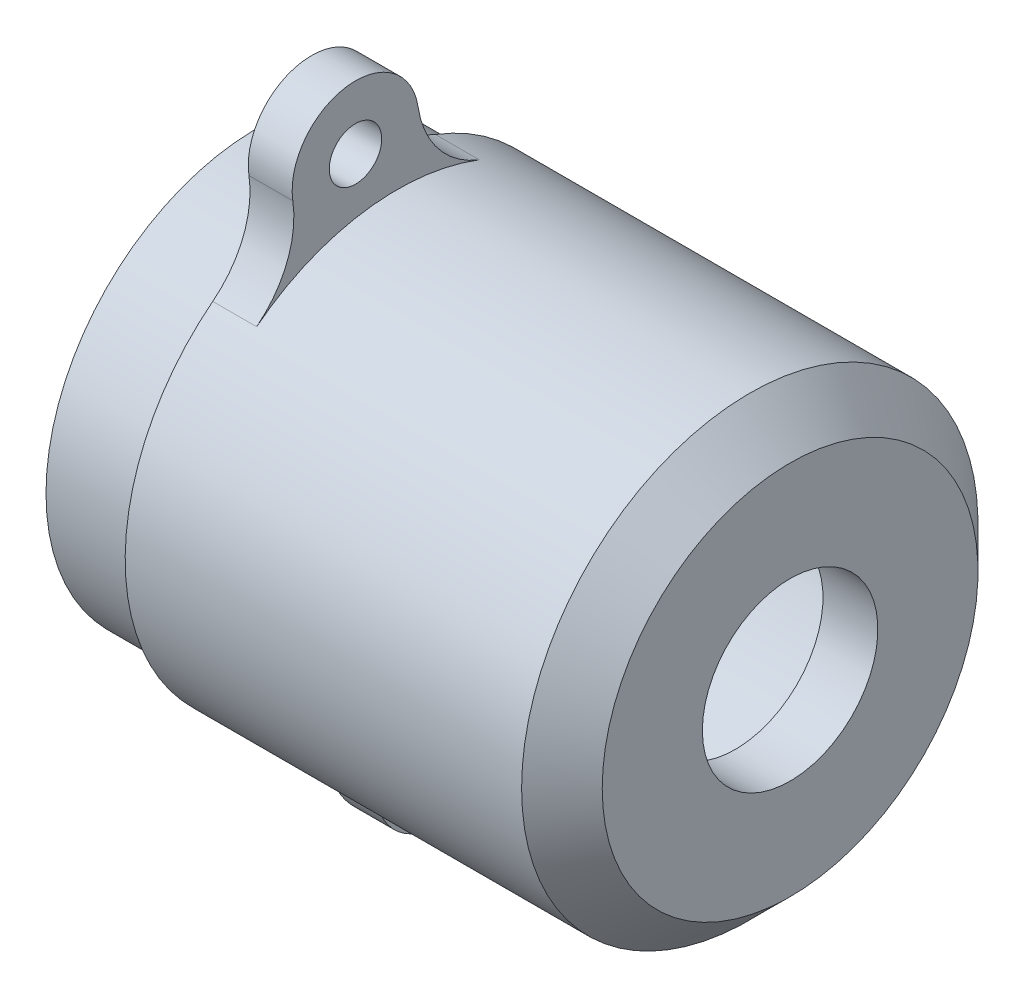
SolidWorks part; units mm, degrees
material "6061-T6 (SS)"
ref_plane "Front Plane" through (0, 0, 0) normal (0, 0, 1) x (1, 0, 0)
ref_plane "Top Plane" through (0, 0, 0) normal (0, 1, 0) x (1, 0, 0)
ref_plane "Right Plane" through (0, 0, 0) normal (1, 0, 0) x (0, 0, -1)
other "Center of Mass"
sketch "Sketch1" plane through (-25.4, 0, 0) normal (1, 0, 0) x (0, 0, -1)
  line L0 (0, 0) -> (-3.0235, 20.259) construction
  line L1 (-0.1715, 16.6719) -> (1.509, 20.9354) construction
  line L2 (1.509, 20.9354) -> (-1.3431, 24.5225) construction
  line L3 (-1.3431, 24.5225) -> (-5.8756, 23.846) construction
  line L4 (-5.8756, 23.846) -> (-7.5561, 19.5825) construction
  line L5 (-7.5561, 19.5825) -> (-4.704, 15.9955) construction
  line L6 (-4.704, 15.9955) -> (-0.1715, 16.6719) construction
  line L7 (4.704, -15.9955) -> (0.1715, -16.6719) construction
  line L8 (0.1715, -16.6719) -> (-1.509, -20.9354) construction
  line L9 (-1.509, -20.9354) -> (1.3431, -24.5225) construction
  line L10 (1.3431, -24.5225) -> (5.8756, -23.846) construction
  line L11 (5.8756, -23.846) -> (7.5561, -19.5825) construction
  line L12 (7.5561, -19.5825) -> (4.704, -15.9955) construction
  line L13 (-7.5561, 19.5825) -> (1.509, 20.9354) construction
  line L15 (0, 0) -> (12.0871, 1.8039) construction
  circle A0 centre (0, 0) radius 13.9746
  circle A1 centre (0, 0) radius 16.5146 construction
  circle A3 centre (3.0235, -20.259) radius 3.9688 construction
  circle A4 centre (-3.0235, 20.259) radius 8.6143 construction
  arc A8 (-10.1777, 13.0056) -> (-5.9368, -15.4106) centre (0, 0) ccw
  arc A9 (5.9368, 15.4106) -> (10.1777, -13.0056) centre (0, 0) cw
  circle A16 centre (-3.0235, 20.259) radius 2.667 construction
  circle A17 centre (3.0235, -20.259) radius 2.667 construction
  arc A18 (-9.6563, 36.4316) -> (-11.3683, 23.9475) centre (128.3504, 11.1461) ccw construction
  arc A19 (4.4855, 36.4316) -> (4.6428, 28.4562) centre (76.9323, 33.8717) ccw construction
  arc A20 (-10.1777, 13.0056) -> (-7.5561, 19.5825) centre (-14.5121, 18.5444) ccw
  arc A21 (-7.5561, 19.5825) -> (1.509, 20.9354) centre (-3.0235, 20.259) cw
  arc A22 (1.509, 20.9354) -> (5.9368, 15.4106) centre (8.4651, 21.9736) ccw
  arc A23 (7.5561, -19.5825) -> (10.1777, -13.0056) centre (14.5121, -18.5444) cw
  arc A24 (-1.509, -20.9354) -> (7.5561, -19.5825) centre (3.0235, -20.259) ccw
  arc A25 (-5.9368, -15.4106) -> (-1.509, -20.9354) centre (-8.4651, -21.9736) cw
  point P4 (-2.4377, 16.3337)
  dimension "D1" = 27.9492
  dimension "D4" = 5.334
  dimension "D2" = 2.54
  dimension "D3" = 7.9375
extrude "Boss-Extrude1" add sketch "Sketch1" along normal blind 3.175
sketch "Sketch2" plane through (-22.225, 0, 0) normal (1, 0, 0) x (0, 0, -1)
  circle A0 centre (0, 0) radius 13.9746
  circle A1 centre (0, 0) radius 16.5146
  arc A2 (-10.1777, 13.0056) -> (-5.9368, -15.4106) centre (0, 0) ccw construction
  circle A3 centre (0, 0) radius 13.9746 construction
extrude "Boss-Extrude2" add sketch "Sketch2" along normal up to surface (24.4625 mm away)
sketch "Sketch5" plane through (0, 0, 0) normal (0, 0, 1) x (1, 0, 0)
  line L1 (6.2063, 13.598) -> (6.2063, 6.35)
  line L3 (2.2375, -16.5146) -> (2.2375, 16.5146) construction
  line L4 (2.2375, 6.35) -> (2.2375, 16.5146)
  line L5 (0, 0) -> (45.5597, 0) construction
  line L6 (2.2375, 6.35) -> (6.2063, 6.35)
  line L7 (2.2375, 16.5146) -> (3.2896, 16.5146)
  line L8 (3.2896, 16.5146) -> (6.2063, 13.598)
  line L9 (2.2375, 13.9746) -> (4.0336, 15.7707) construction
  dimension "D2" = 3.9688
  dimension "D1" = 12.7
  dimension "D3" = 45
  dimension "D4" = 2.54
  dimension "D5" = 2.54
revolve "Revolve1" add sketch "Sketch5" angle 360 about L5
sketch "Sketch3" plane through (-25.4, 0, 0) normal (-1, 0, 0) x (0, 0, 1)
  circle A0 centre (0, 0) radius 13.9746
  circle A1 centre (0, 0) radius 15.2446
  circle A2 centre (0, 0) radius 13.9746 construction
  dimension "D1" = 1.27
extrude "Boss-Extrude3" add sketch "Sketch3" along normal blind 7
sketch "Sketch6" plane through (0, 0, 0) normal (0, 0, 1) x (1, 0, 0)
  line L0 (-25.4, -24.8417) -> (-24.5043, -24.8417)
  line L1 (-25.4, -24.8417) -> (-22.225, -24.8417) construction
  line L2 (-25.4, -24.8417) -> (-25.4, -21.59)
  line L3 (-25.4, -19.5825) -> (-25.4, -24.8417) construction
  arc A0 (-25.4, -21.59) -> (-22.3418, -27.0202) centre (-19.05, -21.59) ccw construction
  arc A1 (-24.5043, -24.8417) -> (-25.4, -21.59) centre (-19.05, -21.59) cw
extrude "Cut-Extrude1" cut sketch "Sketch6" against normal through all both and the other way through all
hole_wizard "#6 Clearance Hole1" positions "Sketch7" profile "Sketch8" hole size "#6" standard "ANSI Inch" end condition up to next
sketch "Sketch7" plane through (-22.225, 0, 0) normal (1, 0, 0) x (0, 0, -1)
  point P0 (-3.0235, 20.259)
  point P3 (3.0235, -20.259)
sketch "Sketch8" plane through (-22.225, 20.259, 3.0235) normal (0, 1, 0) x (0, 0, -1)
  line L0 (0, 0) -> (0, 3.175)
  line L1 (0, 3.175) -> (1.8986, 3.175)
  line L2 (1.8986, 3.175) -> (1.8986, 0)
  line L5 (1.8986, 0) -> (0, 0)
  line L11 (0, -6.35) -> (0, 107.95) construction
  dimension "Thru Hole Dia." = 3.7973
  dimension "Thru Hole Depth" = 3.175
equation "\"motor diameter\"= 28mm"
equation "\"D1@Sketch1\"=\"motor diameter\"-0.002in"
equation "\"D1@Boss-Extrude3\"=7mm"
equation "\"D2@Sketch5\"=5/32"
